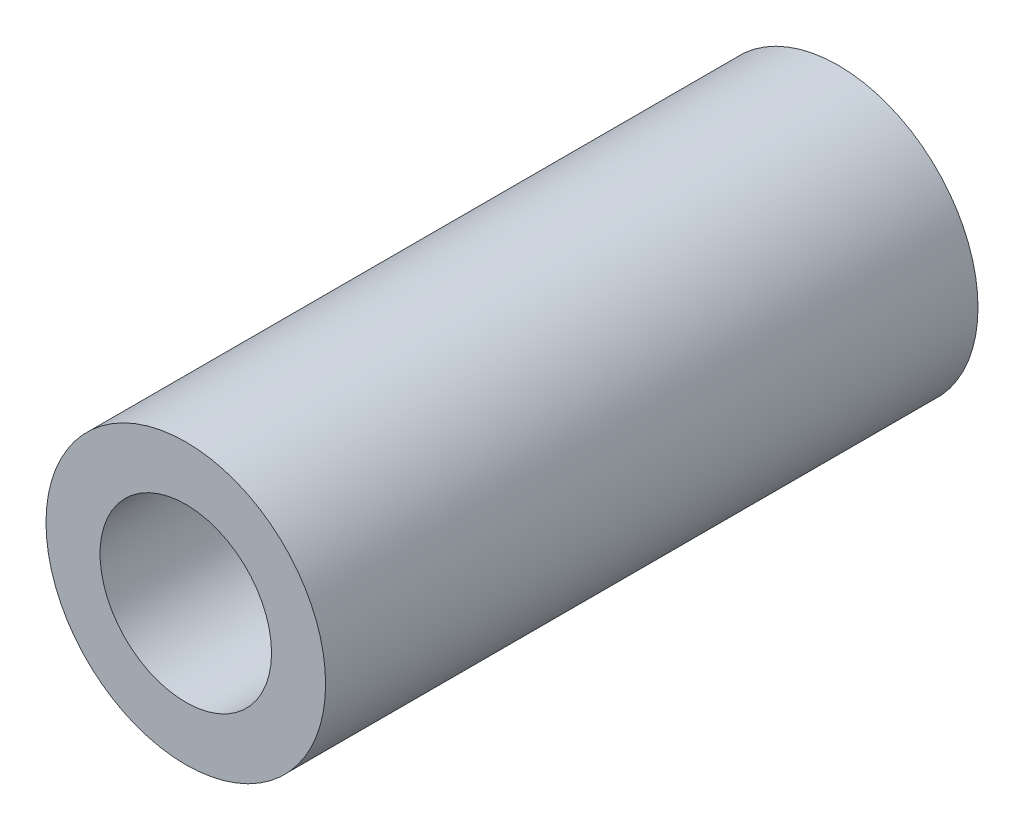
SolidWorks part; units mm, degrees
ref_plane "Front Plane" through (0, 0, 0) normal (0, 0, 1) x (1, 0, 0)
ref_plane "Top Plane" through (0, 0, 0) normal (0, 1, 0) x (1, 0, 0)
ref_plane "Right Plane" through (0, 0, 0) normal (1, 0, 0) x (0, 0, -1)
sketch "Sketch1" plane through (0, 0, 0) normal (0, 0, 1) x (1, 0, 0)
  circle A0 centre (0, 0) radius 2.3812
  circle A1 centre (0, 0) radius 1.4605
  dimension "OD" = 4.7625
  dimension "ID" = 2.921
extrude "Extrude1" add sketch "Sketch1" along normal mid plane 11.1125
sketch "Sketch2" plane through (0, 0, 0) normal (1, 0, 0) x (0, 0, -1)
  line L0 (-5.5562, -1.4605) -> (5.5562, -1.4605) construction
  line L3 (5.5562, 1.4605) -> (-5.5562, 1.4605) construction
  line L5 (-5.5562, -1.4605) -> (5.5562, -1.4605)
  line L6 (5.5562, 1.4605) -> (-5.5562, 1.4605)
sketch "Sketch4" plane through (0, 0, 5.5562) normal (0, 0, 1) x (1, 0, 0)
  line L0 (0, 0) -> (-1.0327, 1.0327)
  line L1 (0, -0.8731) -> (0, 0.8731) construction
  circle A0 centre (0, 0) radius 1.4605 construction
  dimension "D1" = 45
